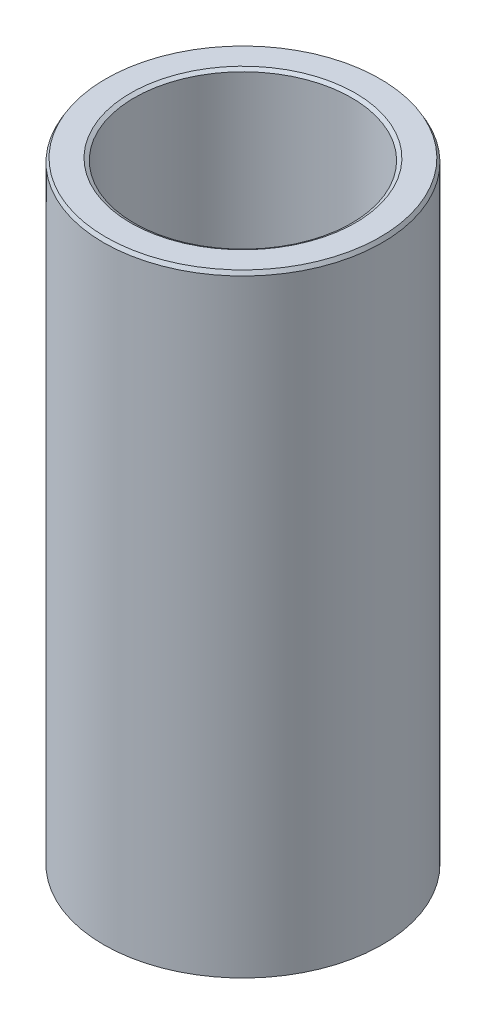
SolidWorks part; units mm, degrees
ref_plane "Front Plane" through (0, 0, 0) normal (0, 0, 1) x (1, 0, 0)
ref_plane "Top Plane" through (0, 0, 0) normal (0, 1, 0) x (1, 0, 0)
ref_plane "Right Plane" through (0, 0, 0) normal (1, 0, 0) x (0, 0, -1)
sketch "Sketch1" plane through (0, 0, 0) normal (0, 1, 0) x (1, 0, 0)
  circle A0 centre (0, 0) radius 60
  dimension "SLEEVE_OD" = 120
extrude "Boss-Extrude1" add sketch "Sketch1" along normal blind 264.4047
sketch "Sketch2" plane through (0, 0, 0) normal (0, 1, 0) x (1, 0, 0)
  circle A0 centre (0, 0) radius 46.8054
  dimension "BORE_D" = 93.6108
extrude "Cut-Extrude1" cut sketch "Sketch2" along normal through all
chamfer "Chamfer1" distance 1.6143 angle 30 4 edges at (0, 264.4047, 46.8054) (0, 0, 46.8054) (0, 0, 60) (0, 264.4047, 60) first distance on face at (0, 264.4047, 46.8054) first distance on face at (0, 0, 46.8054) first distance on face at (0, 264.4047, 60)
